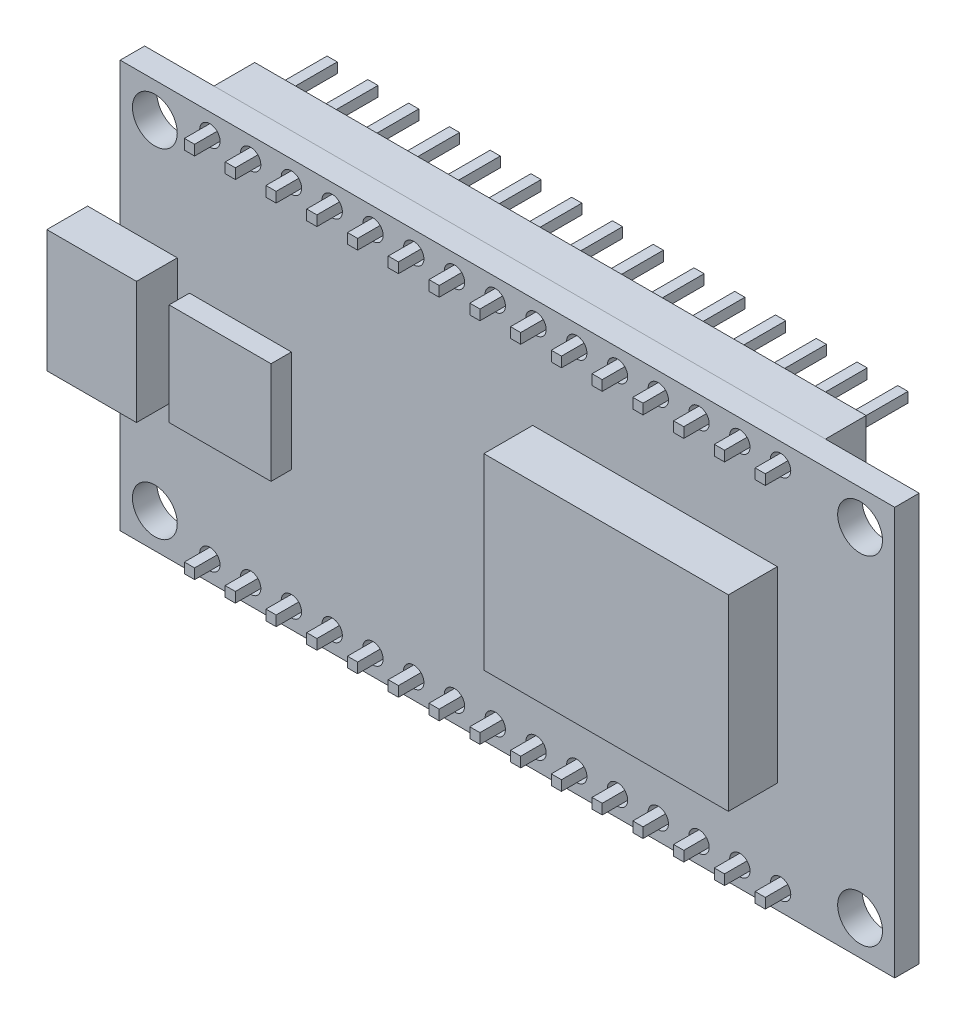
SolidWorks part; units mm, degrees
ref_plane "Front Plane" through (0, 0, 0) normal (0, 0, 1) x (1, 0, 0)
ref_plane "Top Plane" through (0, 0, 0) normal (0, 1, 0) x (1, 0, 0)
ref_plane "Right Plane" through (0, 0, 0) normal (1, 0, 0) x (0, 0, -1)
sketch "Sketch1" plane through (0, 0, 0) normal (0, 0, 1) x (1, 0, 0)
  line L1 (0, 0) -> (48.26, 0)
  line L2 (0, 0) -> (0, 25.4)
  line L3 (0, 25.4) -> (48.26, 25.4)
  line L4 (48.26, 0) -> (48.26, 25.4)
  dimension "D1" = 48.26
  dimension "D2" = 25.4
extrude "Boss-Extrude1" add sketch "Sketch1" along normal blind 1.524
sketch "Sketch2" plane through (0, 0, 1.524) normal (0, 0, 1) x (1, 0, 0)
  line L0 (2.159, 2.159) -> (2.159, 23.241) construction
  line L1 (2.159, 23.241) -> (46.101, 23.241) construction
  line L2 (46.101, 23.241) -> (46.101, 2.159) construction
  line L3 (46.101, 2.159) -> (2.159, 2.159) construction
  line L4 (24.13, 23.241) -> (24.13, 25.4) construction
  line L5 (48.26, 25.4) -> (0, 25.4) construction
  line L6 (2.159, 12.7) -> (0, 12.7) construction
  line L7 (0, 25.4) -> (0, 0) construction
  circle A0 centre (2.159, 23.241) radius 1.397
  circle A1 centre (46.101, 23.241) radius 1.397
  circle A2 centre (46.101, 2.159) radius 1.397
  circle A3 centre (2.159, 2.159) radius 1.397
  dimension "D1" = 2.794
  dimension "D2" = 21.082
  dimension "D3" = 43.942
extrude "Cut-Extrude1" cut sketch "Sketch2" against normal through all
sketch "Sketch3" plane through (0, 0, 1.524) normal (0, 0, 1) x (1, 0, 0)
  line L0 (40.9448, 12.7) -> (48.26, 12.7) construction
  line L1 (25.7048, 18.542) -> (40.9448, 18.542)
  line L2 (25.7048, 18.542) -> (25.7048, 6.858)
  line L3 (25.7048, 6.858) -> (40.9448, 6.858)
  line L4 (40.9448, 18.542) -> (40.9448, 6.858)
  line L5 (48.26, 0) -> (48.26, 25.4) construction
  line L6 (0, 12.7) -> (3.556, 12.7) construction
  line L7 (-2.032, 16.51) -> (3.556, 16.51)
  line L8 (-2.032, 16.51) -> (-2.032, 8.89)
  line L9 (-2.032, 8.89) -> (3.556, 8.89)
  line L10 (3.556, 16.51) -> (3.556, 8.89)
  line L11 (0, 25.4) -> (0, 0) construction
  line L12 (0, 0) -> (48.26, 0) construction
  line L13 (4.318, 14.986) -> (10.668, 14.986)
  line L14 (4.318, 14.986) -> (4.318, 8.636)
  line L15 (4.318, 8.636) -> (10.668, 8.636)
  line L16 (10.668, 14.986) -> (10.668, 8.636)
  dimension "D1" = 15.24
  dimension "D2" = 11.684
  dimension "D3" = 7.3152
  dimension "D4" = 7.62
  dimension "D5" = 5.588
  dimension "D6" = 2.032
  dimension "D7" = 6.35
  dimension "D8" = 6.35
  dimension "D9" = 0.762
  dimension "D10" = 8.636
extrude "Boss-Extrude2" add sketch "Sketch3" along normal blind 3.048 contours L3 L4 L1 L2
extrude "Boss-Extrude3" add sketch "Sketch3<3>" along normal blind 2.54 contours L9 L10 L7 L8
sketch "Sketch3<3>" plane through (0, 0, 1.524) normal (0, 0, 1) x (1, 0, 0) same geometry as "Sketch3"
extrude "Boss-Extrude4" add sketch "Sketch3<4>" along normal blind 1.27 contours L15 L16 L13 L14
sketch "Sketch3<4>" plane through (0, 0, 1.524) normal (0, 0, 1) x (1, 0, 0) same geometry as "Sketch3"
sketch "Sketch4" plane through (0, 0, 1.524) normal (0, 0, 1) x (1, 0, 0)
  line L0 (0, 25.4) -> (0, 16.51) construction
  line L1 (5.588, 24.13) -> (5.588, 1.27) construction
  line L2 (5.588, 12.7) -> (48.26, 12.7) construction
  circle A0 centre (5.588, 24.13) radius 0.635
  circle A1 centre (5.588, 1.27) radius 0.635
  dimension "D1" = 1.27
  dimension "D2" = 1.27
  dimension "D3" = 5.588
  dimension "D4" = 22.86
extrude "Cut-Extrude2" cut sketch "Sketch4" against normal through all and the other way through all
pattern_linear "LPattern1" count 15 spacing 2.54 along (1, 0, 0) of "Cut-Extrude2"
sketch "Sketch5" plane through (0, 0, 0) normal (0, 0, -1) x (-1, 0, 0)
  line L0 (-5.588, 24.13) -> (-4.318, 24.13) construction
  line L1 (-42.418, 25.4) -> (-4.318, 25.4)
  line L2 (-42.418, 25.4) -> (-42.418, 22.86)
  line L3 (-42.418, 22.86) -> (-4.318, 22.86)
  line L4 (-4.318, 25.4) -> (-4.318, 22.86)
  line L5 (0, 0) -> (-48.26, 0) construction
  line L6 (-42.418, 0) -> (-4.318, 0)
  line L7 (-42.418, 0) -> (-42.418, 2.54)
  line L8 (-42.418, 2.54) -> (-4.318, 2.54)
  line L9 (-4.318, 0) -> (-4.318, 2.54)
  circle A0 centre (-41.148, 24.13) radius 0.635 construction
  dimension "D3" = 1.27
  dimension "D1" = 2.54
  dimension "D2" = 1.27
extrude "Boss-Extrude5" add sketch "Sketch5" along normal blind 2.54 separate body
ref_plane "Plane1" through (0, 0, 2.794) normal (0, 0, 1) x (1, 0, 0)
sketch "Sketch6" plane through (0, 0, 2.794) normal (0, 0, 1) x (1, 0, 0)
  line L1 (5.2705, 24.4475) -> (5.9055, 24.4475)
  line L2 (5.2705, 24.4475) -> (5.2705, 23.8125)
  line L3 (5.2705, 23.8125) -> (5.9055, 23.8125)
  line L4 (5.9055, 24.4475) -> (5.9055, 23.8125)
  line L5 (5.2705, 24.4475) -> (5.9055, 23.8125) construction
  line L6 (5.2705, 23.8125) -> (5.9055, 24.4475) construction
  line L7 (5.2705, 1.5875) -> (5.9055, 1.5875)
  line L8 (5.2705, 1.5875) -> (5.2705, 0.9525)
  line L9 (5.2705, 0.9525) -> (5.9055, 0.9525)
  line L10 (5.9055, 1.5875) -> (5.9055, 0.9525)
  line L11 (5.2705, 1.5875) -> (5.9055, 0.9525) construction
  line L12 (5.2705, 0.9525) -> (5.9055, 1.5875) construction
  point P0 (5.588, 24.13)
  point P6 (5.588, 1.27)
  dimension "D1" = 0.635
  dimension "D2" = 0.635
  dimension "D3" = 0.635
  dimension "D4" = 0.635
extrude "Boss-Extrude6" add sketch "Sketch6" against normal blind 8.89 separate body
pattern_linear "LPattern2" count 15 spacing 2.54 along (1, 0, 0) of "Boss-Extrude6"
